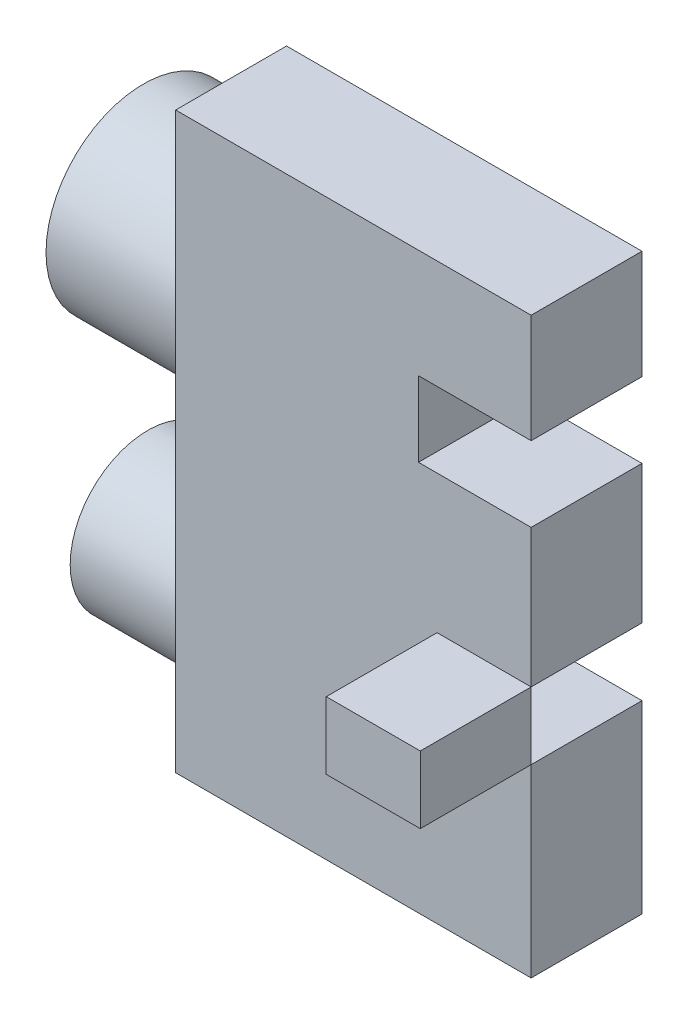
SolidWorks part; units mm, degrees
ref_plane "前视基准面" through (0, 0, 0) normal (0, 0, 1) x (1, 0, 0)
ref_plane "上视基准面" through (0, 0, 0) normal (0, 1, 0) x (1, 0, 0)
ref_plane "右视基准面" through (0, 0, 0) normal (1, 0, 0) x (0, 0, -1)
sketch "草图2" plane through (0, 0, 0) normal (0, 0, 1) x (1, 0, 0)
  line L0 (0, 0) -> (32.0669, 0)
  line L1 (0, 0) -> (0, 51.7801)
  line L2 (0, 51.7801) -> (32.0669, 51.7801)
  line L3 (32.0669, 51.7801) -> (32.0669, 0)
extrude "凸台-拉伸1" add sketch "草图2" along normal blind 10
sketch "草图3" plane through (0, 0, 0) normal (0, 0, 1) x (1, 0, 0)
  line L0 (0, 42.3501) -> (-12.9177, 42.3501)
  line L1 (0, 51.7801) -> (0, 0) construction
  line L2 (-12.9177, 42.3501) -> (-12.9177, 33.5714)
  line L3 (-12.9177, 33.5714) -> (0, 33.5714)
  line L4 (0, 33.5714) -> (0, 42.3501)
revolve "旋转1" add sketch "草图3" angle 360 about L3
sketch "草图4" plane through (0, 0, 0) normal (0, 0, 1) x (1, 0, 0)
  line L0 (0, 51.7801) -> (0, 0) construction
  line L1 (-12.5123, 15.5003) -> (0, 15.5003)
  line L2 (-12.5123, 15.5003) -> (-12.5123, 8.4961)
  line L3 (-12.5123, 8.4961) -> (0, 8.4961) construction
  line L4 (0, 15.5003) -> (0, 8.4961)
  line L5 (0, 8.4961) -> (-12.5123, 8.4961)
revolve "旋转2" add sketch "草图4" angle 360 about L3
sketch "草图5" plane through (0, 0, 10) normal (0, 0, 1) x (1, 0, 0)
  line L0 (32.0669, 0) -> (32.0669, 51.7801) construction
  line L1 (21.9022, 41.9766) -> (32.0669, 41.9766)
  line L2 (21.9022, 41.9766) -> (21.9022, 35.2058)
  line L3 (21.9022, 35.2058) -> (32.0669, 35.2058)
  line L4 (32.0669, 41.9766) -> (32.0669, 35.2058)
  line L6 (23.5832, 22.7381) -> (32.0669, 22.7381)
  line L7 (23.5832, 22.7381) -> (23.5832, 16.6677)
  line L8 (23.5832, 16.6677) -> (32.0669, 16.6677)
  line L9 (32.0669, 22.7381) -> (32.0669, 16.6677)
  line M3 (32.0669, 0) -> (32.0669, 51.7801)
extrude "切除-拉伸1" cut sketch "草图5" against normal blind 10 contours L2 L3 L1 M3 | L7 L6 L9 L8 region at (26.9845, 38.5912, 10)
extrude "凸台-拉伸2" add sketch "草图5<3>" along normal blind 10 separate body contours L7 L8 L6 M3 region at (27.825, 19.7029, 10)
sketch "草图5<3>" plane through (0, 0, 10) normal (0, 0, 1) x (1, 0, 0) same geometry as "草图5"
